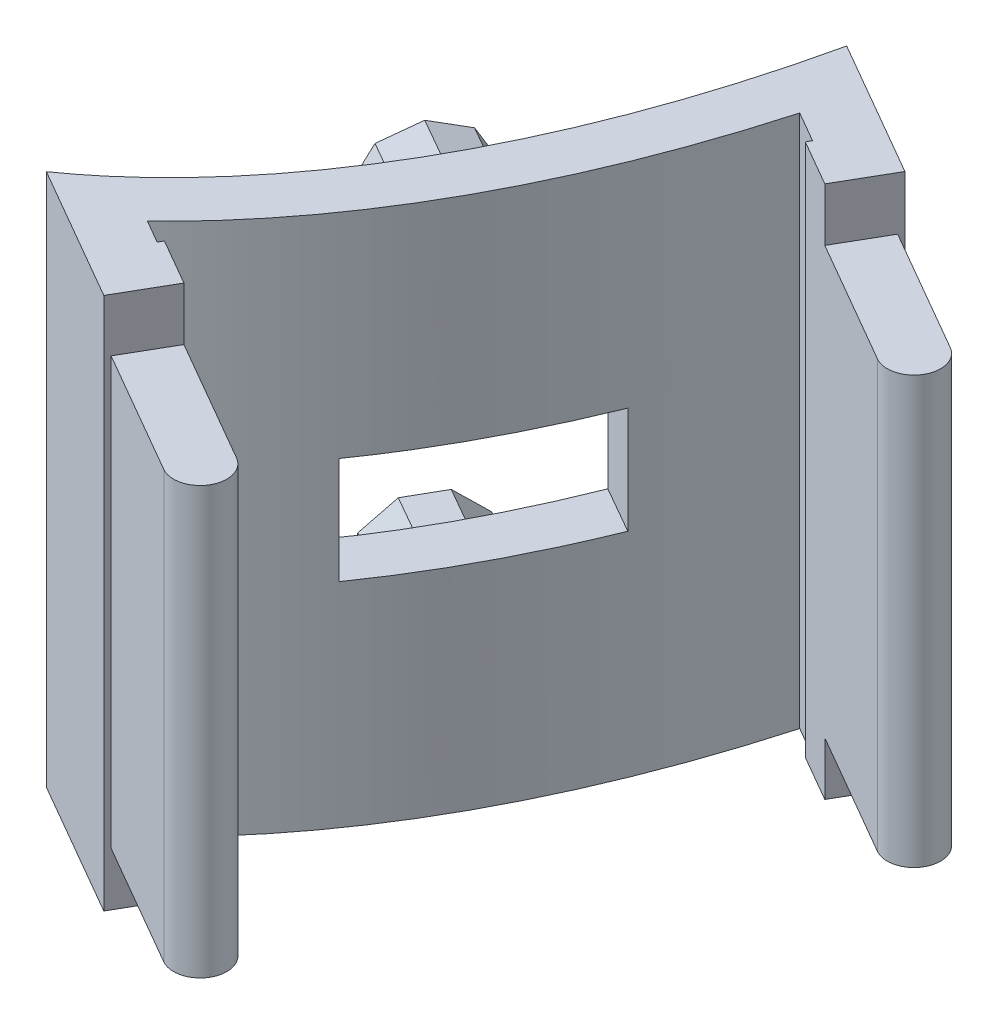
SolidWorks part; units mm, degrees
ref_plane "Front Plane" through (0, 0, 0) normal (0, 0, 1) x (1, 0, 0)
ref_plane "Top Plane" through (0, 0, 0) normal (0, 1, 0) x (1, 0, 0)
ref_plane "Right Plane" through (0, 0, 0) normal (1, 0, 0) x (0, 0, -1)
sketch "Sketch1" plane through (0, 0, 0) normal (0, 1, 0) x (1, 0, 0)
  line L0 (-15, 79.6562) -> (15, 79.6562)
  line L9 (-15, 75.1314) -> (-42.5, 27.5)
  line L10 (-42.5, 27.5) -> (-42.5, -27.5)
  line L11 (-42.5, -27.5) -> (-15, -75.1314)
  line L12 (-15, -75.1314) -> (15, -75.1314)
  line L13 (15, -75.1314) -> (42.5, -27.5)
  line L14 (42.5, -27.5) -> (42.5, 27.5)
  line L15 (42.5, 27.5) -> (15, 75.1314)
  line L16 (15, 75.1314) -> (-15, 75.1314)
  line L17 (-49.2865, 0) -> (49.2865, 0) construction
  line L18 (-15, 75.1314) -> (-15, 79.6562) construction
  line L19 (15, 75.1314) -> (15, 79.6562) construction
  line L20 (-15, 75.1314) -> (-18.7805, 77.3141) construction
  line L21 (-42.5, 27.5) -> (-46.1003, 29.5787) construction
  line L22 (-42.5, 27.5) -> (-46.5452, 27.5) construction
  line L23 (-42.5, -27.5) -> (-46.5452, -27.5) construction
  line L24 (-42.5, -27.5) -> (-46.1003, -29.5787) construction
  line L25 (-15, -75.1314) -> (-18.7805, -77.3141) construction
  line L26 (-15, -75.1314) -> (-15, -79.6562) construction
  line L27 (15, -75.1314) -> (15, -79.6562) construction
  line L28 (15, -75.1314) -> (18.7805, -77.3141) construction
  line L29 (42.5, -27.5) -> (46.1003, -29.5787) construction
  line L30 (42.5, -27.5) -> (46.5452, -27.5) construction
  line L31 (42.5, 27.5) -> (46.5452, 27.5) construction
  line L32 (42.5, 27.5) -> (46.1003, 29.5787) construction
  line L33 (15, 75.1314) -> (18.7805, 77.3141) construction
  line L34 (-15, -79.6562) -> (15, -79.6562)
  line L35 (18.7805, 77.3141) -> (46.1003, 29.5787) construction
  line L36 (46.5452, 27.5) -> (46.5452, -27.5) construction
  line L37 (46.1003, -29.5787) -> (18.7805, -77.3141) construction
  line L39 (-18.7805, -77.3141) -> (-46.1003, -29.5787) construction
  line L40 (-46.5452, -27.5) -> (-46.5452, 27.5) construction
  line L41 (-18.7805, 77.3141) -> (-46.1003, 29.5787) construction
  line L42 (0, 79.6562) -> (0, -79.6562) construction
  ellipse E0 centre (0, 0) end of major axis (0, 79.6261) minor radius 45.2865
  ellipse E1 centre (0, 0) end of major axis (0, 83.623) minor radius 49.2865 (-15, 79.6562) -> (-15, -79.6562) ccw
  ellipse E2 centre (0, 0) end of major axis (0, 83.623) minor radius 49.2865 (15, -79.6562) -> (15, 79.6562) ccw
  dimension "D1" = 55
  dimension "D2" = 30
  dimension "D3" = 150
  dimension "D4" = 150
  dimension "D5" = 150
  dimension "D6" = 150
  dimension "D7" = 90
ref_plane "Plane1" through (0, 0, 0) normal (0, 1, 0) x (1, 0, 0)
sketch "Sketch2" plane through (0, 0, 0) normal (0, 1, 0) x (1, 0, 0)
  line L0 (18.7805, -77.3141) -> (23.043, -79.775)
  line L1 (23.043, -79.775) -> (50.3628, -32.0396) construction
  line L2 (46.1003, -29.5787) -> (50.3628, -32.0396)
  line L3 (58.773, -37.4726) -> (72.6295, -45.4726)
  line L4 (46.1003, -29.5787) -> (18.7805, -77.3141) construction
  line L5 (72.6295, -45.4726) -> (45.6295, -92.238)
  line L6 (15, -75.1314) -> (18.7805, -77.3141) construction
  line L7 (42.5, -27.5) -> (46.1003, -29.5787) construction
  line L8 (50.3628, -32.0396) -> (59.023, -37.0396)
  line L9 (58.773, -37.4726) -> (31.773, -84.238) construction
  line L10 (31.523, -84.671) -> (23.043, -79.775)
  line L11 (45.6295, -92.238) -> (31.773, -84.238)
  line L12 (59.023, -37.0396) -> (58.773, -37.4726)
  line L13 (31.773, -84.238) -> (31.523, -84.671)
  ellipse E0 centre (0, 0) end of major axis (0, 83.623) minor radius 49.2865 (18.7805, -77.3141) -> (46.1003, -29.5787) ccw
  ellipse E1 centre (0, 0) end of major axis (0, 83.623) minor radius 49.2865 (15, -79.6562) -> (15, 79.6562) ccw construction
  dimension "D1" = 0.5
  dimension "D2" = 0.5
extrude "Boss-Extrude1" add sketch "Sketch2" along normal blind 50
shell "Shell1" thickness 5 removed face at (45.8938, 0, 61.6041) removed face at (59.1295, 25, 68.8553) removed face at (45.8938, 50, 61.6041)
ref_plane "Plane2" through (47.4776, 0, 27.1722) normal (-0.8679, 0, -0.4967) x (-0.4967, 0, 0.8679)
sketch "Sketch3" plane through (47.4776, 0, 27.1722) normal (-0.8679, 0, -0.4967) x (-0.4967, 0, 0.8679)
  line L0 (30.2729, 50) -> (30.2729, 0) construction
  line L1 (57.7731, 50) -> (2.7727, 50) construction
  line L2 (29.1136, 0) -> (-29.1136, 0) construction
  line L3 (2.7727, 25) -> (57.7731, 25) construction
  line L4 (2.7727, 50) -> (2.7727, 0) construction
  line L5 (57.7731, 50) -> (57.7731, 0) construction
  line L7 (25.6649, 37.3396) -> (28.453, 35)
  line L8 (28.453, 35) -> (32.0927, 35)
  line L9 (32.0927, 35) -> (34.8809, 37.3396)
  line L10 (34.8809, 37.3396) -> (35.5129, 40.924)
  line L11 (35.5129, 40.924) -> (33.6931, 44.076)
  line L12 (33.6931, 44.076) -> (30.2729, 45.3209)
  line L13 (30.2729, 45.3209) -> (26.8527, 44.076)
  line L14 (26.8527, 44.076) -> (25.0328, 40.924)
  line L15 (25.0328, 40.924) -> (25.6649, 37.3396)
  line L16 (33.6931, 5.924) -> (35.5129, 9.076)
  line L17 (35.5129, 9.076) -> (34.8809, 12.6604)
  line L18 (34.8809, 12.6604) -> (32.0927, 15)
  line L19 (32.0927, 15) -> (28.453, 15)
  line L20 (28.453, 15) -> (25.6649, 12.6604)
  line L21 (25.6649, 12.6604) -> (25.0328, 9.076)
  line L22 (25.0328, 9.076) -> (26.8527, 5.924)
  line L23 (26.8527, 5.924) -> (30.2729, 4.6791)
  line L24 (30.2729, 4.6791) -> (33.6931, 5.924)
  circle A0 centre (30.2729, 40) radius 5 construction
  circle A1 centre (30.2729, 10) radius 5 construction
  dimension "D1" = 10
  dimension "D2" = 10
sketch "Sketch4" plane through (47.4776, 0, 27.1722) normal (-0.8679, 0, -0.4967) x (-0.4967, 0, 0.8679)
  line L0 (30.2729, 50) -> (30.2729, 0) construction
  line L1 (40.2729, 20) -> (20.2729, 20)
  line L2 (40.2729, 20) -> (40.2729, 30)
  line L3 (40.2729, 30) -> (20.2729, 30)
  line L4 (20.2729, 20) -> (20.2729, 30)
  line L5 (40.2729, 20) -> (20.2729, 30) construction
  line L6 (40.2729, 30) -> (20.2729, 20) construction
  point P0 (30.2729, 25)
extrude "Boss-Extrude2" add sketch "Sketch3" along normal blind 5.5 and the other way blind 7.5
extrude "Cut-Extrude1" cut sketch "Sketch4" against normal blind 10
sketch "Sketch5" plane through (-28.5328, 0, 49.4203) normal (-0.5, 0, 0.866) x (0.866, 0, 0.5)
  line L0 (85.6352, 50) -> (85.6352, 0) construction
  line L1 (69.6352, 50) -> (85.6352, 50)
  line L2 (69.6352, 50) -> (69.6352, 45)
  line L3 (69.6352, 45) -> (85.6352, 45)
  line L4 (85.6352, 50) -> (85.6352, 45)
  line L5 (29.1136, 0) -> (-29.1136, 0) construction
  line L6 (69.6352, 0) -> (85.6352, 0)
  line L7 (69.6352, 0) -> (69.6352, 5)
  line L8 (69.6352, 5) -> (85.6352, 5)
  line L9 (85.6352, 0) -> (85.6352, 5)
  line L10 (69.6352, 50) -> (69.6352, 0) construction
  line L11 (69.6352, 50) -> (69.6352, 0) construction
extrude "Cut-Extrude2" cut sketch "Sketch5" against normal through all
fillet "Fillet2" 2 edges at (45.6295, 25, 92.238) (48.1295, 25, 87.9078) type full round first side face at (38.7012, 25, 88.238) second side face at (36.6546, 25, 81.2828) middle face at (46.8795, 25, 90.0729)
fillet "Fillet3" 2 edges at (70.1295, 25, 49.8027) (72.6295, 25, 45.4726) type full round first side face at (58.6546, 25, 43.1777) second side face at (65.7012, 25, 41.4726) middle face at (71.3795, 25, 47.6377)
